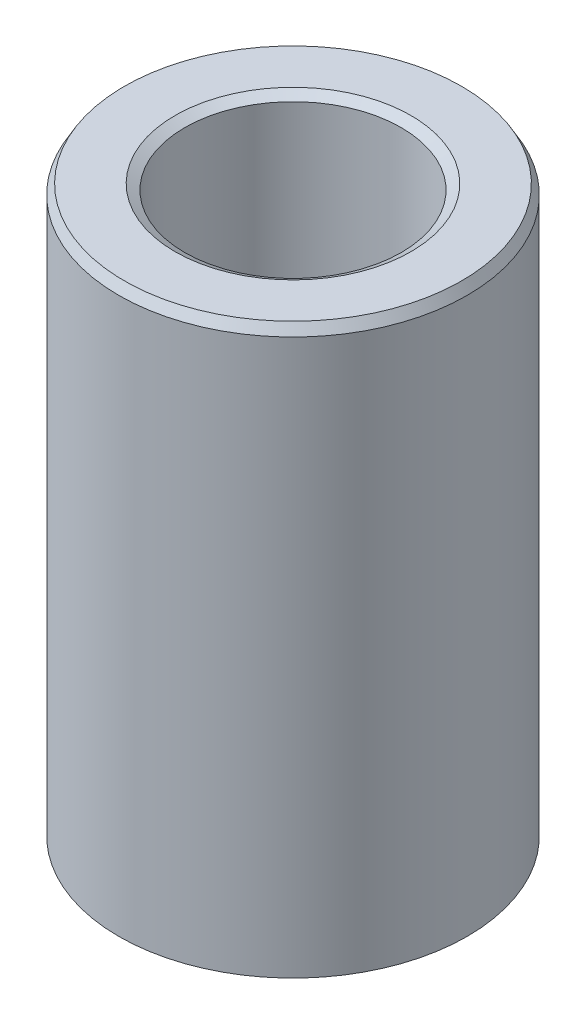
SolidWorks part; units mm, degrees
ref_plane "Front Plane" through (0, 0, 0) normal (0, 0, 1) x (1, 0, 0)
ref_plane "Top Plane" through (0, 0, 0) normal (0, 1, 0) x (1, 0, 0)
ref_plane "Right Plane" through (0, 0, 0) normal (1, 0, 0) x (0, 0, -1)
sketch "Sketch1" plane through (0, 0, 0) normal (0, 1, 0) x (1, 0, 0)
  circle A0 centre (0, 0) radius 22.5
  dimension "SLEEVE_OD" = 45
extrude "Boss-Extrude1" add sketch "Sketch1" along normal blind 73.686
sketch "Sketch2" plane through (0, 0, 0) normal (0, 1, 0) x (1, 0, 0)
  circle A0 centre (0, 0) radius 13.9816
  dimension "BORE_D" = 27.9633
extrude "Cut-Extrude1" cut sketch "Sketch2" along normal through all
chamfer "Chamfer1" distance 1.2559 angle 30 4 edges at (0, 73.686, 13.9816) (0, 0, 13.9816) (0, 0, 22.5) (0, 73.686, 22.5) first distance on face at (0, 73.686, 13.9816) first distance on face at (0, 0, 13.9816) first distance on face at (0, 73.686, 22.5)
